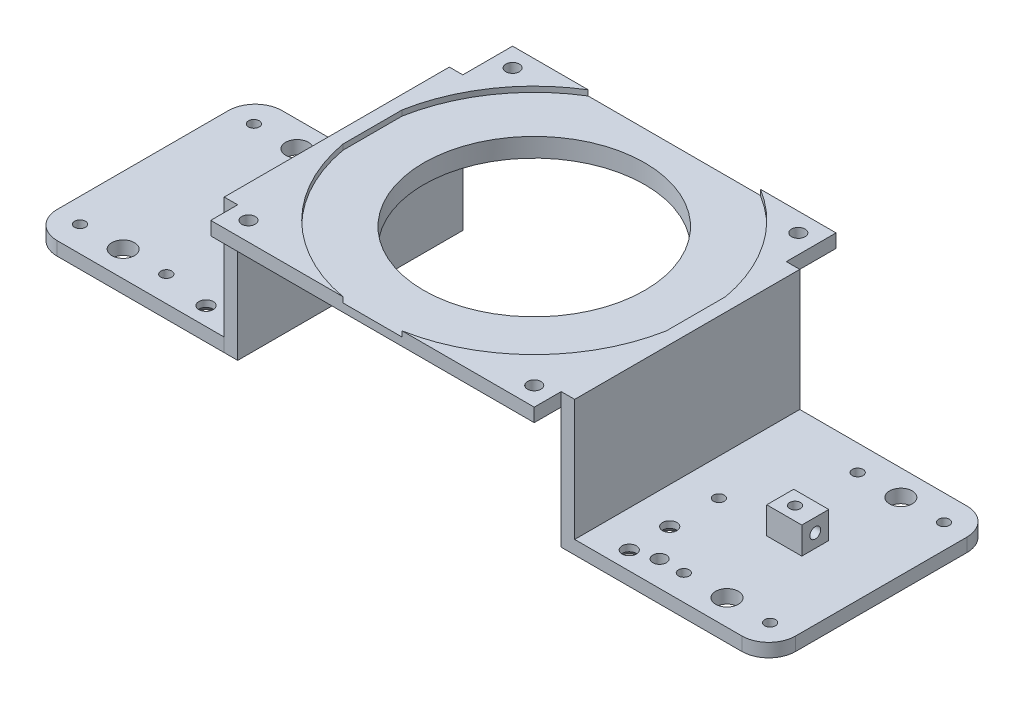
SolidWorks part; units mm, degrees
ref_plane "Front Plane" through (0, 0, 0) normal (0, 0, 1) x (1, 0, 0)
ref_plane "Top Plane" through (0, 0, 0) normal (0, 1, 0) x (1, 0, 0)
ref_plane "Right Plane" through (0, 0, 0) normal (1, 0, 0) x (0, 0, -1)
sketch "Sketch1" plane through (0, 0, 0) normal (0, 1, 0) x (1, 0, 0)
  line L12 (-60, -30) -> (-60, 30)
  line L15 (0, -44.5314) -> (0, 44.5314) construction
  line L16 (60, -30) -> (60, 30)
  line L21 (-60, 40) -> (-60, 30)
  line L22 (-60, -30) -> (-60, -40)
  line L24 (60, 30) -> (60, 40)
  line L27 (60, -40) -> (60, -30)
  line L30 (-30, 51.9615) -> (-60, 51.9615)
  line L31 (-60, 51.9615) -> (-60, 40)
  line L32 (0, -60) -> (-60, -60)
  line L33 (-60, -60) -> (-60, -40)
  line L34 (0, -60) -> (60, -60)
  line L35 (60, -60) -> (60, -40)
  line L36 (30, 51.9615) -> (60, 51.9615)
  line L37 (60, 51.9615) -> (60, 40)
  line L38 (-30, 51.9615) -> (30, 51.9615)
  circle A0 centre (0, 0) radius 41
  point P4 (-60, 0)
  point P18 (60, 0)
  point P29 (-60, 40)
  point P32 (-60, -40)
  point P35 (60, 40)
  point P38 (60, -40)
  dimension "D6" = 60
  dimension "D9" = 41
ref_axis "Axis1" through (0, 45.0144, 0) along (0, -1, 0)
extrude "Boss-Extrude6" add sketch "Sketch1" along normal blind 5
sketch "Sketch51" plane through (0, 5, 0) normal (0, 1, 0) x (1, 0, 0)
  circle A0 centre (0, 0) radius 61
  dimension "D1" = 122
extrude "Cut-Extrude10" cut sketch "Sketch51" against normal blind 2
sketch "Sketch52" plane through (0, 5, 0) normal (0, 1, 0) x (1, 0, 0)
  line L0 (-60, -60) -> (-11, -60) construction
  line L1 (-60, -11) -> (-60, -60) construction
  line L2 (-31.9531, 51.9615) -> (-60, 51.9615) construction
  line L3 (-60, 51.9615) -> (-60, 11) construction
  line L4 (0, -44.5314) -> (0, 44.5314) construction
  circle A0 centre (-53, -53) radius 2.5
  circle A1 centre (-53, 44.9615) radius 2.5
  circle A2 centre (53, -53) radius 2.5
  circle A3 centre (53, 44.9615) radius 2.5
  dimension "D1" = 5
  dimension "D2" = 7
  dimension "D3" = 7
  dimension "D4" = 5
  dimension "D5" = 7
  dimension "D6" = 7
extrude "Cut-Extrude11" cut sketch "Sketch52" against normal through all
ref_plane "Plane2" through (0, -30, 0) normal (0, 1, 0) x (1, 0, 0)
sketch "Sketch39" plane through (0, 5, 0) normal (0, 1, 0) x (1, 0, 0)
  line L0 (-31.9531, 51.9615) -> (-60, 51.9615) construction
  line L1 (-65, 33.5015) -> (-60, 33.5015)
  line L2 (-65, 33.5015) -> (-65, -50)
  line L3 (-65, -50) -> (-60, -50)
  line L4 (-60, 33.5015) -> (-60, -50)
  line L5 (-60, -60) -> (-11, -60) construction
  dimension "D1" = 5
  dimension "D2" = 18.46
  dimension "D3" = 10
extrude "Boss-Extrude10" add sketch "Sketch39" against normal blind 50
mirror "Mirror1" about plane through (0, 0, 0) normal (1, 0, 0) of "Boss-Extrude10"
sketch "Sketch41" plane through (0, -45, 0) normal (0, -1, 0) x (1, 0, 0)
  line L3 (-65, 50) -> (-137, 50)
  line L4 (-65, -33.5015) -> (-137, -33.5015)
  line L5 (-137, -33.5015) -> (-137, 50)
  line L6 (0, -44.5314) -> (0, 44.5314) construction
  line L7 (-65, 50) -> (-65, -33.5015)
  line L8 (-112, -24) -> (-137, -24) construction
  line L10 (-71.4146, 0) -> (-98.1159, 0) construction
  line L11 (44.5314, 0) -> (-44.5314, 0) construction
  line L12 (-65, -33.5015) -> (-65, 50) construction
  circle A2 centre (-112, -24) radius 4.2
  circle A6 centre (-128, -24) radius 2
  circle A10 centre (-96, -24) radius 2
  circle A14 centre (-112, 40.5) radius 4.2
  circle A15 centre (-128, 40.5) radius 2
  circle A16 centre (-96, 40.5) radius 2
  dimension "D2" = 16
  dimension "D5" = 8.4
  dimension "D8" = 4
  dimension "D4" = 2
  dimension "D7" = 16
  dimension "D1" = 137
  dimension "D3" = 24
  dimension "D6" = 25
extrude "Boss-Extrude11" add sketch "Sketch41" against normal blind 5 separate body
fillet "Fillet1" radius 10 2 edges at (-137, -42.5, 50) (-137, -42.5, -33.5015)
hole_wizard "CSK for M5 Flat Head Machine Screw2" positions "Sketch49" profile "Sketch50" countersink size "M5" standard "ANSI Metric" end condition through all
sketch "Sketch49" plane through (0, -45, 0) normal (0, -1, 0) x (-1, 0, 0)
  line L0 (65, -50) -> (127, -50) construction
  line L1 (60, -50) -> (60, 33.5015) construction
  point P0 (78.5, -43.25)
  point P2 (78.5, -28.25)
  dimension "D1" = 6.75
  dimension "D2" = 15
  dimension "D3" = 18.5
sketch "Sketch50" plane through (-78.5, -45, 43.25) normal (1, 0, 0) x (0, 0, -1)
  line L0 (0, 0) -> (0, 50)
  line L1 (0, 50) -> (2.65, 50)
  line L2 (2.65, 50) -> (2.65, 2.55)
  line L3 (2.65, 2.55) -> (5.2, 0)
  line L5 (5.2, 0) -> (0, 0)
  line L6 (-2.65, 2.55) -> (-5.2, 0) construction
  line L11 (0, -6.35) -> (0, 107.95) construction
  dimension "Thru Hole Dia." = 5.3
  dimension "Thru Hole Depth" = 50
  dimension "Near C'Sink Dia." = 10.4
  dimension "Near C'Sink Angle" = 90
mirror "Mirror6" about plane through (0, 0, 0) normal (1, 0, 0) of "CSK for M5 Flat Head Machine Screw2", "Fillet1", "Boss-Extrude11"
sketch "Sketch43" plane through (0, -40, 0) normal (0, 1, 0) x (1, 0, 0)
  line L1 (0, -44.5314) -> (0, 44.5314) construction
  line L3 (60, -50) -> (60, 33.5015) construction
  line L4 (127, -50) -> (60, -50) construction
  line L5 (65, -50) -> (127, -50) construction
  circle A0 centre (105, -8.25) radius 3.5
  circle A3 centre (78.5, -10) radius 2
  circle A4 centre (87, -40.5) radius 2.5
  circle A5 centre (112, -40.5) radius 4.2 construction
  dimension "D1" = 105
  dimension "D2" = 7
  dimension "D4" = 4
  dimension "D5" = 18.5
  dimension "D6" = 40
  dimension "D7" = 25
  dimension "D8" = 9.5
  dimension "D9" = 5
  dimension "D10" = 41.75
extrude "Cut-Extrude5" cut sketch "Sketch43" against normal blind 10
sketch "Sketch44" plane through (0, -40, 0) normal (0, 1, 0) x (1, 0, 0)
  line L8 (99.5, -3.25) -> (112.5, -3.25)
  line L9 (99.5, -3.25) -> (99.5, -13.25)
  line L10 (99.5, -13.25) -> (112.5, -13.25)
  line L11 (112.5, -3.25) -> (112.5, -13.25)
  line L12 (99.5, -3.25) -> (112.5, -13.25) construction
  line L13 (99.5, -13.25) -> (112.5, -3.25) construction
  circle A0 centre (105, -8.25) radius 2
  point P3 (106, -8.25)
  dimension "D2" = 10
  dimension "D4" = 4
  dimension "D1" = 1
  dimension "D3" = 13
extrude "Boss-Extrude12" add sketch "Sketch44" along normal blind 10 separate body
sketch "Sketch45" plane through (112.5, 0, 0) normal (-1, 0, 0) x (0, 0, 1)
  line L0 (13.25, -30) -> (3.25, -30) construction
  line L3 (8.25, -35) -> (8.25, -30) construction
  circle A0 centre (8.25, -35) radius 2
  dimension "D1" = 4
extrude "Cut-Extrude6" cut sketch "Sketch45" along normal blind 8
sketch "Sketch46" plane through (0, 0, 0) normal (0, -1, 0) x (1, 0, 0)
  circle A0 centre (0, 0) radius 41
  circle A1 centre (0, 0) radius 45
  dimension "D1" = 90
extrude "Boss-Extrude13" add sketch "Sketch46" along normal blind 4
sketch "Sketch53" plane through (0, 0, 0) normal (0, -1, 0) x (1, 0, 0)
  circle A0 centre (0, 0) radius 43
  circle A1 centre (0, 0) radius 45
  dimension "D1" = 90
  dimension "D2" = 86
extrude "Cut-Extrude12" cut sketch "Sketch53" along normal blind 2
